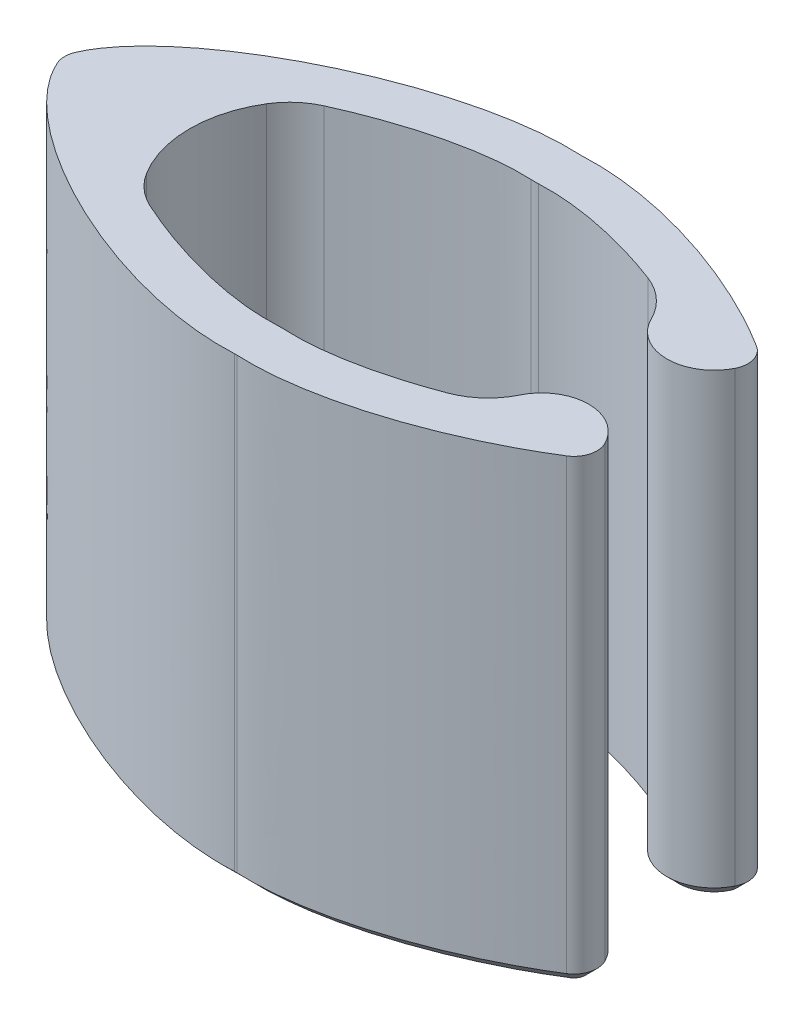
SolidWorks part; units mm, degrees
ref_plane "Front Plane" through (0, 0, 0) normal (0, 0, 1) x (1, 0, 0)
ref_plane "Top Plane" through (0, 0, 0) normal (0, 1, 0) x (1, 0, 0)
ref_plane "Right Plane" through (0, 0, 0) normal (1, 0, 0) x (0, 0, -1)
sketch "Sketch1" plane through (0, 0, 0) normal (0, 1, 0) x (1, 0, 0)
  line L0 (-7.5, 0) -> (7.5, 0)
  line L1 (-7.5, 0) -> (-7.5, 7.5) construction
  spline S0 degree 3 poles (-7.5, 7.5) (-2.0319, 7.8113) (6.5199, 3.4547) (7.5, 0) knots 0.45293 0.45293 0.45293 0.45293 1 1 1 1
  spline S1 degree 3 poles (-7.5, 7.5) (-12.9681, 7.8113) (-21.5199, 3.4547) (-22.5, 0) knots 0.45293 0.45293 0.45293 0.45293 1 1 1 1
  spline S2 degree 3 poles (-7.5, -7.5) (-2.0319, -7.8113) (6.5199, -3.4547) (7.5, 0) knots 0.45293 0.45293 0.45293 0.45293 1 1 1 1
  spline S3 degree 3 poles (-7.5, -7.5) (-12.9681, -7.8113) (-21.5199, -3.4547) (-22.5, 0) knots 0.45293 0.45293 0.45293 0.45293 1 1 1 1
  point P4 (0, 0)
  dimension "D1" = 15
  dimension "D2" = 7.5
extrude "Boss-Extrude1" add sketch "Sketch1" along normal blind 20 contours S2 S3 S1 S0
fillet "Fillet1" radius 1 4 edges at (-22.5, 10, 0) (-7.5, 10, -7.5) (7.5, 10, 0) (-7.5, 10, 7.5)
shell "Shell1" thickness 2 removed face at (-7.5, 0, 0) removed face at (-7.5, 20, 0)
sketch "Sketch3" plane through (0, 0, 0) normal (1, 0, 0) x (0, 0, -1)
  line L1 (-3.75, 20) -> (3.75, 20)
  line L2 (-3.75, 20) -> (-3.75, 0)
  line L3 (-3.75, 0) -> (3.75, 0)
  line L4 (3.75, 20) -> (3.75, 0)
  line L6 (-0.4029, 20) -> (-7.5158, 20) construction
  point P4 (-3.3328, 20)
  point P6 (0, 0)
  point P8 (0, 0)
  dimension "D1" = 7.5
extrude "Cut-Extrude1" cut sketch "Sketch3" along normal up to next
sketch "Sketch4" plane through (0, 20, 0) normal (0, 1, 0) x (1, 0, 0)
  line L0 (4.1012, 3.75) -> (0.0035, 3.75) construction
  line L2 (4.1012, -3.75) -> (0.0035, -3.75) construction
  circle A0 centre (2.0524, 3.75) radius 2.0489
  circle A1 centre (2.0524, -3.75) radius 2.0489
  spline S1 degree 3 poles (2475.1853, -1672.2652) (-2736.5409, 1556.0265) (2839.9383, -1350.5233) (-2785.1448, 1103.1154) knots -2.805829 -2.805829 -2.805829 -2.805829 4.159265 4.159265 4.159265 4.159265 only from (-7.4486, 7.5028) to (4.1012, 3.75) construction
  spline S2 degree 3 poles (-7.4486, 7.5028) (-3.9152, 7.6845) (0.8832, 5.9378) (4.1012, 3.75) knots 0.45464 0.45464 0.45464 0.45464 0.806921 0.806921 0.806921 0.806921
  spline S3 degree 3 poles (2475.1853, 1672.2652) (-2736.5409, -1556.0265) (2839.9383, 1350.5233) (-2785.1448, -1103.1154) knots -2.805829 -2.805829 -2.805829 -2.805829 4.159265 4.159265 4.159265 4.159265 only from (-7.4486, -7.5028) to (4.1012, -3.75) construction
  spline S4 degree 3 poles (-7.4486, -7.5028) (-3.9152, -7.6845) (0.8832, -5.9378) (4.1012, -3.75) knots 0.45464 0.45464 0.45464 0.45464 0.806921 0.806921 0.806921 0.806921
  line M3 (4.1012, -3.75) -> (0.0035, -3.75)
  line M10 (0.0035, 3.75) -> (4.1012, 3.75)
extrude "Boss-Extrude2" add sketch "Sketch4" against normal up to surface (20 mm away) contours A0 M10 | A1 M3 region at (2.0524, 20, -2.8804) region at (2.0524, 20, 2.8804) up to face at (-7.6121, 0, 0)
sketch "Sketch5" plane through (0, 20, 0) normal (0, 1, 0) x (1, 0, 0)
  circle A0 centre (-12, 0) radius 5
  spline S0 degree 3 poles (384.2092, 1955.3216) (43.3965, 40.5451) (12.6987, -8.2306) (-10.0095, -5.3503) (-10.5862, -5.2383) (-11.7305, -4.9594) (-12.2996, -4.7916) (-13.4225, -4.4106) (-14.5226, -3.987) (-15.581, -3.4852) (-16.6175, -2.9423) (-17.1248, -2.6504) (-18.1121, -2.0154) (-18.5927, -1.6733) (-19.2805, -1.0983) (-19.5031, -0.8969) (-29.3929, 9.1705) (-14.151, 42.4893) (1407.6327, 1400.0296) knots -4.618735 -4.618735 -4.618735 -4.618735 0.125 0.125 0.25 0.25 0.375 0.375 0.5 0.625 0.625 0.75 0.75 0.875 0.875 0.9375 0.9375 3.832499 3.832499 3.832499 3.832499 only from (-7.6541, -5.5054) to (-20.2903, 0) construction
  spline S1 degree 3 poles (384.2092, -1955.3216) (43.3965, -40.5451) (12.6987, 8.2306) (-10.0095, 5.3503) (-10.5862, 5.2383) (-11.7305, 4.9594) (-12.2996, 4.7916) (-13.4225, 4.4106) (-14.5226, 3.987) (-15.581, 3.4852) (-16.6175, 2.9423) (-17.1248, 2.6504) (-18.1121, 2.0154) (-18.5927, 1.6733) (-19.2805, 1.0983) (-19.5031, 0.8969) (-29.3929, -9.1705) (-14.151, -42.4893) (1407.6327, -1400.0296) knots -4.618735 -4.618735 -4.618735 -4.618735 0.125 0.125 0.25 0.25 0.375 0.375 0.5 0.625 0.625 0.75 0.75 0.875 0.875 0.9375 0.9375 3.832499 3.832499 3.832499 3.832499 only from (-7.6541, 5.5054) to (-20.2903, 0) construction
  spline S2 degree 3 poles (-7.6541, 5.5054) (-8.2545, 5.5363) (-8.8435, 5.4982) (-10.0095, 5.3503) (-10.5862, 5.2383) (-11.7305, 4.9594) (-12.2996, 4.7916) (-13.4225, 4.4106) (-14.5226, 3.987) (-15.581, 3.4852) (-16.6175, 2.9423) (-17.1248, 2.6504) (-18.1121, 2.0154) (-18.5927, 1.6733) (-19.2805, 1.0983) (-19.5031, 0.8969) (-19.9211, 0.4714) (-20.1184, 0.2477) (-20.2903, 0) knots 0 0 0 0 0.125 0.125 0.25 0.25 0.375 0.375 0.5 0.625 0.625 0.75 0.75 0.875 0.875 0.9375 0.9375 1 1 1 1
  spline S3 degree 3 poles (-7.6541, -5.5054) (-8.2545, -5.5363) (-8.8435, -5.4982) (-10.0095, -5.3503) (-10.5862, -5.2383) (-11.7305, -4.9594) (-12.2996, -4.7916) (-13.4225, -4.4106) (-14.5226, -3.987) (-15.581, -3.4852) (-16.6175, -2.9423) (-17.1248, -2.6504) (-18.1121, -2.0154) (-18.5927, -1.6733) (-19.2805, -1.0983) (-19.5031, -0.8969) (-19.9211, -0.4714) (-20.1184, -0.2477) (-20.2903, 0) knots 0 0 0 0 0.125 0.125 0.25 0.25 0.375 0.375 0.5 0.625 0.625 0.75 0.75 0.875 0.875 0.9375 0.9375 1 1 1 1
  point P2 (0, 0)
  dimension "D2" = 10
  dimension "D1" = 12
extrude "Boss-Extrude4" add sketch "Sketch5" against normal up to surface (20 mm away) contours A0 region at (-17.9205, 20, 0) up to face at (-7.8853, 0, 0)
fillet "Fillet2" radius 3 4 edges at (0.0035, 10, 3.75) (0.0035, 10, -3.75)
fillet "Fillet3" radius 1 2 edges
chamfer "Chamfer1" distance 0.5 angle 45 22 edges at (-7.5, 0, -7.5015) (-22.4384, 0, 0) (-7.5, 0, 7.5015) (3.9536, 0, 3.5511) (-0.4655, 0, 3.7561) (-7.5, 0, 5.5015) (-15.691, 0, 3.2936) (-17, 0, 0) (-15.691, 0, -3.2936) (-7.5, 0, -5.5015) (-0.4655, 0, -3.7561) (3.9536, 0, -3.5511)
equation "\"Length\"= 30"
equation "\"Width\"= 15"
equation "\"D1@Sketch1\"=\"Length\"/2"
equation "\"D2@Sketch1\"=\"Width\"/2"
equation "\"Height\"= 20"
equation "\"D1@Boss-Extrude1\"=\"Height\""
